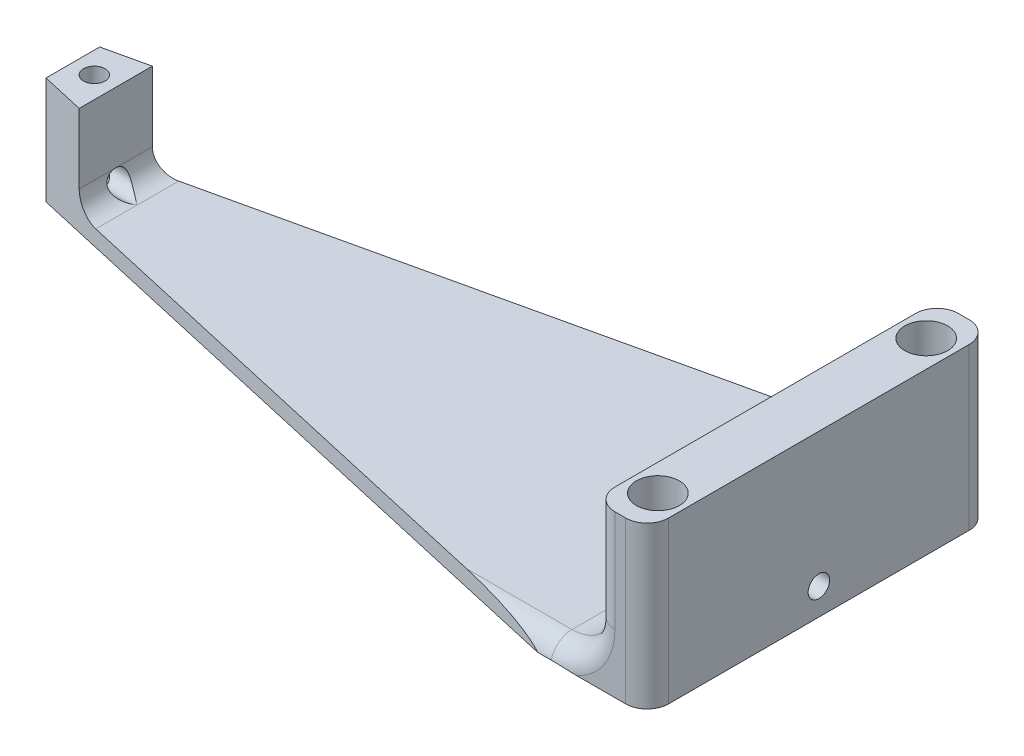
SolidWorks part; units mm, degrees
ref_plane "Front Plane" through (0, 0, 0) normal (0, 0, 1) x (1, 0, 0)
ref_plane "Top Plane" through (0, 0, 0) normal (0, 1, 0) x (1, 0, 0)
ref_plane "Right Plane" through (0, 0, 0) normal (1, 0, 0) x (0, 0, -1)
sketch "Sketch1" plane through (0, 0, 0) normal (0, 0, 1) x (1, 0, 0)
  line L0 (-2, 10) -> (-2, 0)
  line L1 (-2, 0) -> (67.5, 0)
  line L2 (67.5, 0) -> (67.5, 15)
  line L3 (67.5, 15) -> (62.5, 15)
  line L4 (62.5, 15) -> (62.5, 1.5)
  line L5 (62.5, 1.5) -> (2, 1.5)
  line L6 (2, 1.5) -> (2, 10)
  line L7 (2, 10) -> (-2, 10)
  line L8 (2, 10) -> (2, 15) construction
  line L9 (2, 15) -> (62.5, 15) construction
  line L10 (2, 1.5) -> (-2, 1.5) construction
  line L11 (0, 10) -> (0, 0) construction
  line L12 (65, 15) -> (65, 0) construction
  dimension "D1" = 4
  dimension "D2" = 5
  dimension "D3" = 15
  dimension "D4" = 5
  dimension "D5" = 65
  dimension "D6" = 1.5
extrude "Boss-Extrude1" add sketch "Sketch1" along normal mid plane 32
sketch "Sketch2" plane through (0, 15, 0) normal (0, 1, 0) x (1, 0, 0)
  line L0 (-55, 0) -> (55, 0) construction
  line L1 (65, 16) -> (65, -16) construction
  line L2 (67.5, 16) -> (62.5, 16) construction
  line L3 (67.5, -16) -> (62.5, -16) construction
  line L4 (65, 12.5) -> (65, -12.5) construction
  circle A0 centre (65, 12.5) radius 2
  circle A2 centre (65, -12.5) radius 2
  dimension "D1" = 4
  dimension "D2" = 25
extrude "Cut-Extrude1" cut sketch "Sketch2" against normal through all both and the other way through all
sketch "Sketch3" plane through (0, 10, 0) normal (0, 1, 0) x (1, 0, 0)
  circle A0 centre (0, 0) radius 1
  dimension "D1" = 2
extrude "Cut-Extrude2" cut sketch "Sketch3" against normal up to surface (8.5 mm away) up to face at (32.25, 1.5, 0)
fillet "Fillet4" radius 4 1 edges at (62.5, 1.5, 0)
sketch "Sketch4" plane through (2, 0, 0) normal (1, 0, 0) x (0, 0, -1)
  line L0 (-16, 1.5) -> (16, 1.5) construction
  line L1 (-16, 0) -> (-16, 15) construction
  line L2 (16, 0) -> (16, 15) construction
  line L3 (-16, 1.5) -> (16, 1.5) construction
  circle A0 centre (0, 2.5) radius 1
  dimension "D1" = 2
extrude "Cut-Extrude3" cut sketch "Sketch4" against normal through all both and the other way through all
sketch "Sketch5" plane through (0, 1.5, 0) normal (0, 1, 0) x (1, 0, 0)
  line L0 (57.5, 16) -> (-2, 2.5)
  line L1 (58.5, 16) -> (2, 16) construction
  line L2 (-2, -16) -> (-2, 16) construction
  line L4 (-8.25, 0) -> (8.25, 0) construction
  line L5 (57.5, -16) -> (-2, -2.5)
  line L8 (57.5, 16) -> (-2, 16)
  line L9 (-2, 16) -> (-2, 2.5)
  line L10 (-2, -2.5) -> (-2, -16)
  line L11 (-2, -16) -> (57.5, -16)
  dimension "D1" = 5
  dimension "D2" = 5
extrude "Cut-Extrude4" cut sketch "Sketch5" against normal through all both and the other way through all
fillet "Fillet1" radius 2 10 edges at (2, 1.5, 1.7038) (2, 1.5, -1.7038) (67.5, 7.5, -16) (62.5, 10.25, -16) (67.5, 7.5, 16) (62.5, 10.25, 16) (58, 1.5, -16) (61.3284, 2.6716, -16) (58, 1.5, 16) (61.3284, 2.6716, 16)
